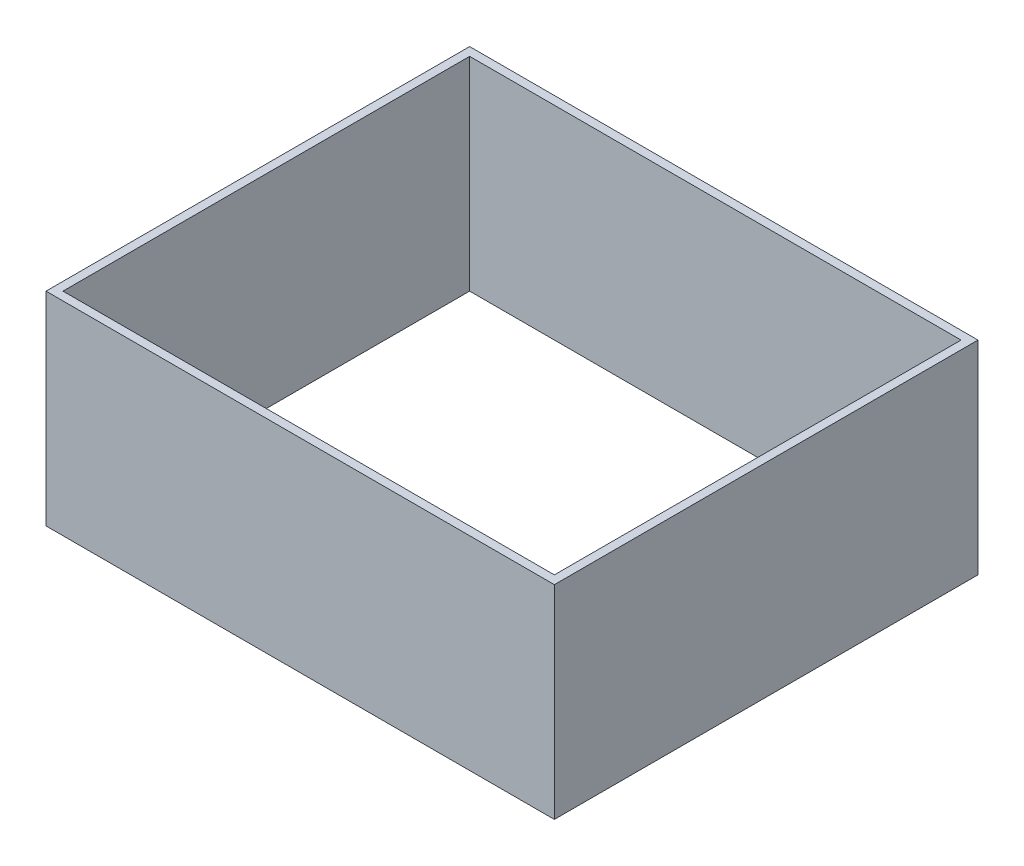
SolidWorks part; units mm, degrees
ref_plane "Front Plane" through (0, 0, 0) normal (0, 0, 1) x (1, 0, 0)
ref_plane "Top Plane" through (0, 0, 0) normal (0, 1, 0) x (1, 0, 0)
ref_plane "Right Plane" through (0, 0, 0) normal (1, 0, 0) x (0, 0, -1)
sketch "Sketch1" plane through (0, 0, 0) normal (0, 1, 0) x (1, 0, 0)
  line L0 (-75, -62.5) -> (-75, 62.5)
  line L1 (0, 0) -> (75, 0) construction
  line L2 (0, -62.5) -> (0, 62.5) construction
  line L3 (-75, 62.5) -> (75, 62.5)
  line L4 (75, -62.5) -> (75, 62.5)
  line L5 (-75, -62.5) -> (-75, 62.5)
  line L6 (75, -62.5) -> (75, 62.5)
  line L7 (-75, -62.5) -> (75, -62.5)
  line L8 (0, 0) -> (-75, 0) construction
  point P10 (-75, 0)
  dimension "D1" = 150
  dimension "D2" = 125
extrude "Boss-Extrude1" add sketch "Sketch1" along normal blind 60 contours L0 L7 L4 L3 region at (0, 0, 0)
shell "Shell1" thickness 2.5 removed face at (0, 0, 0) removed face at (0, 60, 0)
